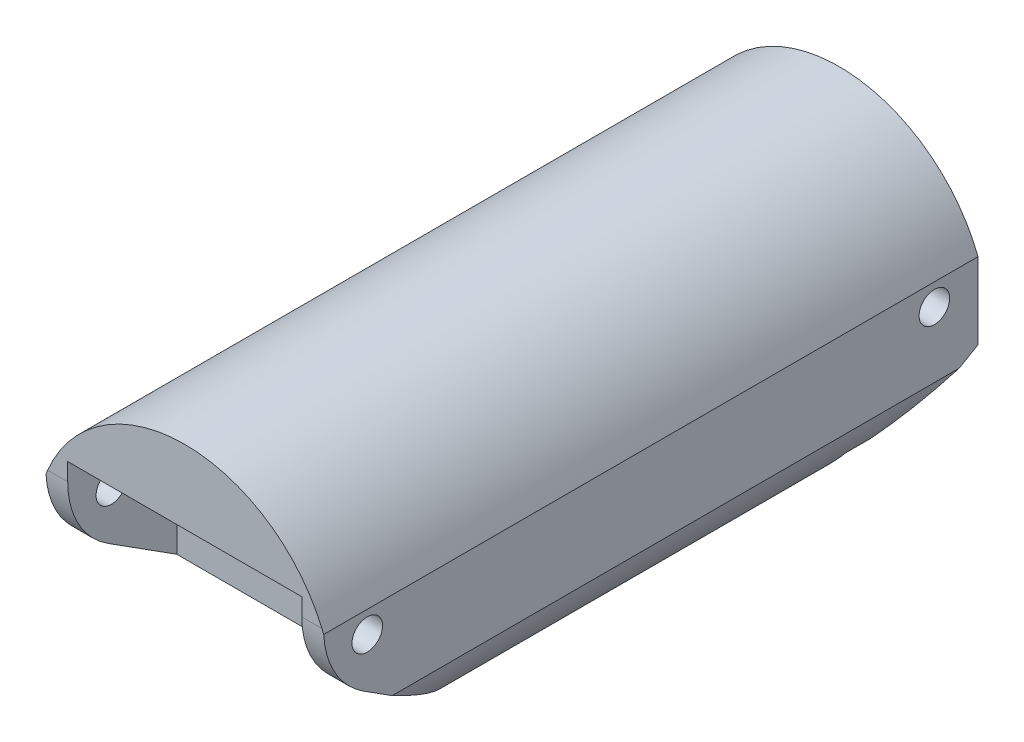
SolidWorks part; units mm, degrees
material "PET"
ref_plane "Front Plane" through (0, 0, 0) normal (0, 0, 1) x (1, 0, 0)
ref_plane "Top Plane" through (0, 0, 0) normal (0, 1, 0) x (1, 0, 0)
ref_plane "Right Plane" through (0, 0, 0) normal (1, 0, 0) x (0, 0, -1)
sketch "Sketch1" plane through (0, 0, 0) normal (0, 0, 1) x (1, 0, 0)
  line L0 (0, 0) -> (0, 5.08)
  line L3 (16.1701, 5.08) -> (16.1701, 0)
  arc A2 (0, 5.08) -> (16.1701, 5.08) centre (8.0851, 1.9583) cw
  arc A3 (0, 0) -> (16.1701, 0) centre (8.0851, 3.1217) ccw
  point P7 (8.0851, -5.5451)
  point P8 (8.0851, 10.6251)
  dimension "D1" = 16.1701
  dimension "D2" = 16.1701
  dimension "D3" = 5.08
extrude "Boss-Extrude1" add sketch "Sketch1" along normal mid plane 38.1 contours A2 L3 A3 L0
sketch "Sketch2" plane through (0, 0, 0) normal (1, 0, 0) x (0, 0, -1)
  line L4 (15.875, 2.54) -> (-49984.125, 2.54) construction
  line L5 (19.05, 5.08) -> (19.05, 0) construction
  line L6 (-19.05, 5.08) -> (-19.05, 0) construction
  line L7 (-19.05, -5.5451) -> (-19.05, 2.54)
  line L8 (-6.35, -5.5451) -> (-19.05, -5.5451)
  line L9 (-19.05, 2.54) -> (-6.35, -5.5451)
  line L10 (0, -1000) -> (0, 49000) construction
  line L18 (19.05, 0.635) -> (19.05, -5.5451)
  line L30 (19.05, -5.5451) -> (8.3458, -5.5451)
  line L31 (-19.05, -5.5451) -> (19.05, -5.5451) construction
  line L32 (8.3458, -5.5451) -> (19.05, 0.635)
  line L33 (-19.05, 10.6251) -> (-19.05, 5.08) construction
  point P11 (19.05, 2.54)
  point P14 (-19.05, 2.54)
  dimension "D1" = 6.35
  dimension "D2" = 2.54
  dimension "D5" = 60
extrude "Cut-Extrude1" cut sketch "Sketch2" along normal through all
sketch "Sketch3" plane through (0, 0, 19.05) normal (0, 0, 1) x (1, 0, 0)
  line L3 (-11.7647, 2.54) -> (36.597, 2.54) construction
  line L4 (8.0851, 9.0576) -> (8.0851, -5.5451) construction
  line L5 (16.1544, 2.54) -> (0, 2.54) construction
  arc A7 (0, 0) -> (16.1701, 0) centre (8.0851, 3.1217) ccw construction
  arc A9 (14.7671, -0.0505) -> (0.9601, 1.1349) centre (8.0851, 3.1217) cw
  arc A13 (5.4415, -3.7866) -> (10.7286, -3.7866) centre (8.0851, -5.5451) cw
extrude "Cut-Extrude2" cut sketch "Sketch3" against normal through all contours A13 A9
ref_plane "Plane1" through (5.08, 0, 0) normal (-1, 0, 0) x (0, 0, 1)
ref_plane "Plane2" through (8.0851, 0, 0) normal (1, 0, 0) x (0, 0, -1)
sketch "Sketch10" plane through (0, 0, 0) normal (-1, 0, 0) x (0, 0, 1)
  line L0 (-19.05, 3.81) -> (-19.05, 0) construction
  line L1 (-19.05, 0.635) -> (-19.05, 5.08) construction
  line L2 (-19.05, 0) -> (-16.3757, 0) construction
  line L4 (15.0602, 0) -> (-17.9501, 0) construction
  circle A1 centre (-16.51, 3.81) radius 0.889
  dimension "D1" = 2.54
  dimension "D2" = 1.778
  dimension "D4" = 3.81
extrude "Cut-Extrude7" cut sketch "Sketch10" against normal through all
ref_plane "Plane3" through (0, 0, 0) normal (0, 0, -1) x (-1, 0, 0)
mirror "Mirror4" about plane through (0, 0, 0) normal (0, 0, -1) of "Cut-Extrude7"
ref_plane "Plane4" through (0, -5.715, 0) normal (0, 1, 0) x (1, 0, 0)
sketch "Sketch17" plane through (0, -5.715, 0) normal (0, 1, 0) x (1, 0, 0)
  line L0 (16.1701, -19.05) -> (0, -19.05) construction
  line L1 (1.27, -19.05) -> (14.9001, -19.05)
  line L2 (1.27, -19.05) -> (1.27, -12.7)
  line L3 (1.27, -12.7) -> (14.9001, -12.7)
  line L4 (14.9001, -19.05) -> (14.9001, -12.7)
  line L5 (-1.5076, 0) -> (24.6013, 0) construction
  line L6 (0, -15.0602) -> (0, -19.05) construction
  line L7 (16.1701, -15.0602) -> (16.1701, -19.05) construction
  line L8 (14.9001, 19.05) -> (14.9001, 12.7)
  line L9 (1.27, 12.7) -> (14.9001, 12.7)
  line L10 (1.27, 19.05) -> (14.9001, 19.05)
  line L11 (1.27, 19.05) -> (1.27, 12.7)
  dimension "D1" = 6.35
  dimension "D2" = 1.27
  dimension "D3" = 1.27
extrude "Cut-Extrude14" cut sketch "Sketch17" along normal blind 12.065
sketch "Sketch18" plane through (0, 0, 12.7) normal (0, 0, 1) x (1, 0, 0)
  line L0 (1.27, -0.508) -> (14.4856, -0.508) construction
  line L1 (5.4181, 8.2296) -> (10.7521, 8.2296) construction
  line L2 (5.4181, 8.2296) -> (5.4181, 2.54) construction
  line L3 (5.4181, 2.54) -> (10.7521, 2.54) construction
  line L4 (10.7521, 8.2296) -> (10.7521, 2.54) construction
  line L5 (5.4181, 8.2296) -> (10.7521, 2.54) construction
  line L6 (5.4181, 2.54) -> (10.7521, 8.2296) construction
  line L7 (1.27, 2.54) -> (0, 2.54) construction
  line L8 (14.9001, 6.35) -> (1.27, 6.35) construction
  line L9 (14.9001, 6.35) -> (1.27, 6.35)
  line L10 (10.1171, 7.8486) -> (10.7521, 7.8486) construction
  line L11 (10.1171, 8.2296) -> (10.7521, 8.2296)
  line L12 (10.1171, 7.4676) -> (10.7521, 7.4676)
  arc A0 (10.1171, 8.2296) -> (10.1171, 7.4676) centre (10.1171, 7.8486) ccw
  arc A1 (10.7521, 7.4676) -> (10.7521, 8.2296) centre (10.7521, 7.8486) ccw
  point P0 (8.0851, 5.3848)
  point P10 (8.0851, 2.54)
  point P13 (8.0851, 6.35)
  point P14 (8.0851, 8.2296)
  point P17 (10.4346, 7.8486)
  dimension "D1" = 3.048
  dimension "D2" = 5.6896
  dimension "D3" = 5.334
  dimension "D4" = 3.048
  dimension "D5" = 0.635
  dimension "D6" = 0.762
extrude "Cut-Extrude15" cut sketch "Sketch18" against normal blind 17.78 contours L12 A1 L11 A0 region at (10.4346, 7.8486, 12.7)
sketch "Sketch19" plane through (0, 0, -12.7) normal (0, 0, -1) x (-1, 0, 0)
  line L0 (-1.27, 6.35) -> (-14.9001, 6.35) construction
  line L1 (-10.7521, 6.0706) -> (-5.4181, 6.0706) construction
  line L2 (-10.7521, 6.0706) -> (-10.7521, 0.381) construction
  line L3 (-10.7521, 0.381) -> (-5.4181, 0.381) construction
  line L4 (-5.4181, 6.0706) -> (-5.4181, 0.381) construction
  line L5 (-10.7521, 6.0706) -> (-5.4181, 0.381) construction
  line L6 (-10.7521, 0.381) -> (-5.4181, 6.0706) construction
  line L7 (-1.27, 6.35) -> (-14.9001, 6.35)
  line L8 (-0.2246, -2.667) -> (-16.7864, -2.667) construction
  line L9 (-1.27, 0.635) -> (0, 0.635) construction
  line L10 (-6.0531, 5.6896) -> (-5.4181, 5.6896) construction
  line L11 (-6.0531, 6.0706) -> (-5.4181, 6.0706)
  line L12 (-6.0531, 5.3086) -> (-5.4181, 5.3086)
  arc A0 (-6.0531, 6.0706) -> (-6.0531, 5.3086) centre (-6.0531, 5.6896) ccw
  arc A1 (-5.4181, 5.3086) -> (-5.4181, 6.0706) centre (-5.4181, 5.6896) ccw
  point P0 (-8.0851, 3.2258)
  point P7 (-8.0851, 6.35)
  point P8 (-8.0851, 6.0706)
  point P15 (-5.7356, 5.6896)
  dimension "D1" = 5.6896
  dimension "D2" = 5.334
  dimension "D3" = 3.302
  dimension "D4" = 3.048
  dimension "D5" = 0.762
  dimension "D6" = 0.635
extrude "Cut-Extrude16" cut sketch "Sketch19" against normal blind 17.78 contours L12 A1 L11 A0 region at (5.7356, 5.6896, -12.7)
fillet "Fillet1" radius 2.54 1 edges at (12.1066, -3.0312, -12.7)
fillet "Fillet2" radius 5.08 2 edges at (0.635, 2.54, 19.05) (15.5351, 2.54, 19.05)
sketch "Sketch20" plane through (0, 0, 0) normal (-1, 0, 0) x (0, 0, 1)
  text T0 "Ring 2"
extrude "Cut-Extrude17" cut sketch "Sketch20" against normal blind 1
sketch "Sketch21" plane through (0, 0, 12.7) normal (0, 0, 1) x (1, 0, 0)
  line L0 (14.9001, 6.35) -> (1.27, 6.35) construction
  line L1 (5.4181, 6.0706) -> (10.7521, 6.0706)
  line L2 (5.4181, 6.0706) -> (5.4181, 0.381)
  line L3 (5.4181, 0.381) -> (10.7521, 0.381)
  line L4 (10.7521, 6.0706) -> (10.7521, 0.381)
  line L5 (5.4181, 6.0706) -> (10.7521, 0.381) construction
  line L6 (5.4181, 0.381) -> (10.7521, 6.0706) construction
  line L7 (14.9001, 6.35) -> (1.27, 6.35)
  line L8 (10.1171, 5.6896) -> (10.7521, 5.6896) construction
  line L9 (10.1171, 6.0706) -> (10.7521, 6.0706)
  line L10 (10.1171, 5.3086) -> (10.7521, 5.3086)
  arc A0 (10.1171, 6.0706) -> (10.1171, 5.3086) centre (10.1171, 5.6896) ccw
  arc A1 (10.7521, 5.3086) -> (10.7521, 6.0706) centre (10.7521, 5.6896) ccw
  point P0 (8.0851, 3.2258)
  point P7 (8.0851, 6.35)
  point P8 (8.0851, 6.0706)
  point P12 (10.4346, 5.6896)
  dimension "D1" = 5.6896
  dimension "D2" = 5.334
  dimension "D3" = 0.381
  dimension "D4" = 0.635
  dimension "D5" = 0.762
extrude "Cut-Extrude18" cut sketch "Sketch21" against normal blind 17.78 contours L1 A0 L10 L4 | L4 A1 region at (10.2811, 5.6896, 12.7) region at (10.9138, 5.6896, 12.7)
equation "\"D1@Sketch1\"=0.6366197724"
equation "\"D2@Sketch1\"=0.6366197724"
equation "\"D1@Boss-Extrude1\"=1.5"
